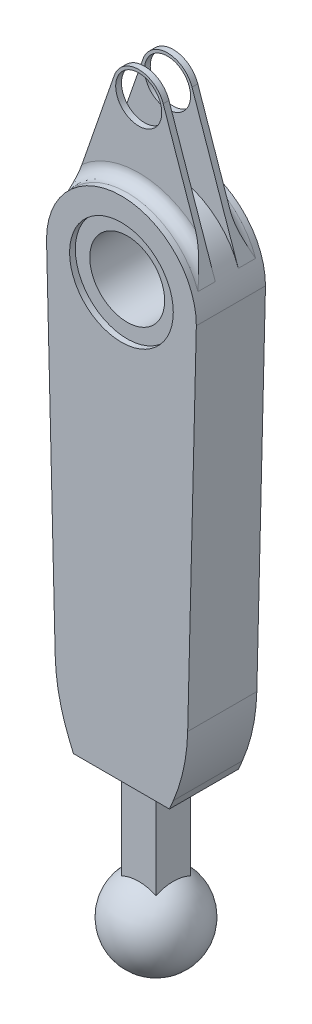
SolidWorks part; units mm, degrees
ref_plane "Front Plane" through (0, 0, 0) normal (0, 0, 1) x (1, 0, 0)
ref_plane "Top Plane" through (0, 0, 0) normal (0, 1, 0) x (1, 0, 0)
ref_plane "Right Plane" through (0, 0, 0) normal (1, 0, 0) x (0, 0, -1)
sketch "Sketch1" plane through (0, 0, 0) normal (0, 0, 1) x (1, 0, 0)
  line L0 (0, 0) -> (0, -50000) construction
  line L1 (-55, 0) -> (-47.5, -308.5609)
  line L2 (-35.7915, -363.12) -> (-35, -365)
  line L3 (35.7915, -363.12) -> (35, -365)
  line L4 (55, 0) -> (47.5, -308.5609)
  line L5 (-35, -365) -> (35, -365)
  line L6 (-21.7855, 135.625) -> (-53.2535, 13.75)
  line L7 (21.7855, 135.625) -> (53.2535, 13.75)
  circle A0 centre (0, 0) radius 55
  arc A1 (-47.5, -308.5609) -> (-35.7915, -363.12) centre (102.4557, -304.916) ccw
  arc A2 (47.5, -308.5609) -> (35.7915, -363.12) centre (-102.4557, -304.916) cw
  circle A3 centre (0, 130) radius 22.5
  circle A4 centre (0, 0) radius 45
  dimension "D1" = 110
  dimension "D2" = 365
  dimension "D4" = 150
  dimension "D7" = 45
  dimension "D9" = 90
  dimension "D3" = 70
  dimension "D5" = 95
  dimension "D6" = 308.5609
  dimension "D8" = 130
extrude "Boss-Extrude1" add sketch "Sketch1" along normal mid plane 10 contours A0 L0 L5 L3 A2 L4 | L0 A0 L1 A1 L2 L5 | L0 A0 L1 A4 | A0 L0 A4 L4 region at (-36.8614, -38.698, 0) region at (25.416, -197.9296, 0) region at (-25.416, -197.9296, 0)
sketch "Sketch3" plane through (0, 0, 5) normal (0, 0, 1) x (1, 0, 0)
  line L0 (35.7915, -363.12) -> (35, -365) construction
  line L1 (-35.7915, -363.12) -> (-35, -365) construction
  line L2 (-35, -365) -> (35, -365) construction
  line L3 (-55, 0) -> (-47.5, -308.5609) construction
  line L4 (55, 0) -> (47.5, -308.5609) construction
  line L5 (35.7915, -363.12) -> (35, -365)
  line L6 (-35.7915, -363.12) -> (-35, -365)
  line L7 (-35, -365) -> (35, -365)
  line L8 (-55, 0) -> (-47.5, -308.5609)
  line L9 (55, 0) -> (47.5, -308.5609)
  line L10 (45.008, -367.0003) -> (41.64, -375)
  line L11 (-41.64, -375) -> (41.64, -375)
  line L12 (-45.008, -367.0003) -> (-41.64, -375)
  line L13 (-64.9999, -0.1266) -> (-57.497, -308.8039)
  line L14 (64.9999, -0.1266) -> (57.497, -308.8039)
  arc A0 (35.7915, -363.12) -> (47.5, -308.5609) centre (-102.4557, -304.916) ccw construction
  arc A1 (-47.5, -308.5609) -> (-35.7915, -363.12) centre (102.4557, -304.916) ccw construction
  arc A2 (55, 0) -> (-55, 0) centre (0, 0) ccw construction
  arc A3 (35.7915, -363.12) -> (47.5, -308.5609) centre (-102.4557, -304.916) ccw
  arc A4 (-47.5, -308.5609) -> (-35.7915, -363.12) centre (102.4557, -304.916) ccw
  arc A5 (55, 0) -> (-55, 0) centre (0, 0) ccw
  arc A6 (-57.497, -308.8039) -> (-45.008, -367.0003) centre (102.4557, -304.916) ccw
  arc A7 (64.9999, -0.1266) -> (-64.9999, -0.1266) centre (0, 0) ccw
  arc A8 (45.008, -367.0003) -> (57.497, -308.8039) centre (-102.4557, -304.916) ccw
  dimension "D1" = 10
extrude "Boss-Extrude5" add sketch "Sketch3" against normal blind 60
sketch "Sketch6" plane through (0, 0, -55) normal (0, 0, -1) x (-1, 0, 0)
  line L0 (-35.7915, -363.12) -> (-35, -365) construction
  line L1 (35, -365) -> (-35, -365) construction
  line L2 (35.7915, -363.12) -> (35, -365) construction
  line L3 (55, 0) -> (47.5, -308.5609) construction
  line L4 (-47.5, -308.5609) -> (-55, 0) construction
  line L5 (-35.7915, -363.12) -> (-35, -365)
  line L6 (35, -365) -> (-35, -365)
  line L7 (35.7915, -363.12) -> (35, -365)
  line L8 (55, 0) -> (47.5, -308.5609)
  line L9 (-47.5, -308.5609) -> (-55, 0)
  arc A0 (35.7915, -363.12) -> (47.5, -308.5609) centre (-102.4557, -304.916) ccw construction
  arc A1 (-47.5, -308.5609) -> (-35.7915, -363.12) centre (102.4557, -304.916) ccw construction
  arc A2 (55, 0) -> (-55, 0) centre (0, 0) ccw construction
  circle A3 centre (0, 0) radius 45 construction
  arc A4 (35.7915, -363.12) -> (47.5, -308.5609) centre (-102.4557, -304.916) ccw
  arc A5 (-47.5, -308.5609) -> (-35.7915, -363.12) centre (102.4557, -304.916) ccw
  arc A6 (55, 0) -> (-55, 0) centre (0, 0) ccw
  circle A7 centre (0, 0) radius 45
extrude "Boss-Extrude6" add sketch "Sketch6" against normal blind 10
sketch "Sketch7" plane through (0, 0, -45) normal (0, 0, 1) x (1, 0, 0)
  circle A0 centre (0, 0) radius 45 construction
  circle A1 centre (0, 0) radius 45
extrude "Boss-Extrude7" add sketch "Sketch7" against normal blind 5
ref_plane "Plane2" through (0, 0, -5) normal (0, 0, -1) x (-1, 0, 0)
sketch "Sketch8" plane through (0, 0, -5) normal (0, 0, -1) x (-1, 0, 0)
  circle A0 centre (0, 0) radius 45 construction
  circle A1 centre (0, 0) radius 45
extrude "Boss-Extrude8" add sketch "Sketch8" against normal blind 5
ref_plane "Plane3" through (0, 0, -25) normal (0, 0, -1) x (-1, 0, 0)
sketch "Sketch9" plane through (0, 0, -25) normal (0, 0, -1) x (-1, 0, 0)
  line L1 (35.7915, -363.12) -> (35, -365) construction
  line L8 (35.7915, -363.12) -> (35, -365)
  line L9 (-21.2636, 137.3558) -> (-61.4283, 21.25)
  line L10 (21.2636, 137.3558) -> (61.4283, 21.25)
  circle A1 centre (0, 130) radius 22.5
  circle A2 centre (0, 130) radius 22.5
  arc A3 (64.9999, -0.1266) -> (-64.9999, -0.1266) centre (0, 0) ccw construction
  arc A5 (61.4283, 21.25) -> (-61.4283, 21.25) centre (0, 0) ccw
  dimension "D1" = 0
extrude "Boss-Extrude9" add sketch "Sketch9" along normal mid plane 30 contours A5 L10 A2 L9 | A2 L10 region at (0, 82.8235, -25) region at (0, 130, -25)
fillet "Fillet1" radius 10 2 edges at (0, 65, -40) (0, 65, -10)
sketch "Sketch13" plane through (0, 0, 0) normal (0, 0, 1) x (1, 0, 0)
  circle A0 centre (0, 0) radius 32.5
  circle A1 centre (0, 0) radius 37.5
  dimension "D1" = 65
  dimension "D2" = 75
extrude "Boss-Extrude11" add sketch "Sketch13" against normal up to surface (50 mm away) contours A0 | A1 up to face at (45, 0, -50)
sketch "Sketch14" plane through (0, 0, 0) normal (0, 0, 1) x (1, 0, 0)
  circle A0 centre (0, 0) radius 32.5
  dimension "D1" = 65
extrude "Cut-Extrude2" cut sketch "Sketch14" against normal through all
sketch "Sketch15" plane through (0, 0, -25) normal (0, 0, -1) x (-1, 0, 0)
  line L0 (-21.2636, 137.3558) -> (-61.4283, 21.25) construction
  line L1 (21.2636, 137.3558) -> (61.4283, 21.25) construction
  line L2 (35.7915, -363.12) -> (35, -365) construction
  line L3 (-21.2636, 137.3558) -> (-61.4283, 21.25)
  line L4 (21.2636, 137.3558) -> (61.4283, 21.25)
  line L5 (35.7915, -363.12) -> (35, -365)
  arc A0 (61.4283, 21.25) -> (-61.4283, 21.25) centre (0, 0) ccw construction
  circle A1 centre (0, 130) radius 22.5
  arc A2 (21.2636, 137.3558) -> (-21.2636, 137.3558) centre (0, 130) ccw
  arc A3 (61.4283, 21.25) -> (-61.4283, 21.25) centre (0, 0) ccw
  dimension "D1" = 0
extrude "Cut-Extrude3" cut sketch "Sketch15" against normal mid plane 20 contours A3 L4 A2 L3 region at (0, 82.8235, -25) region at (0, 130, -25)
sketch "Sketch16" plane through (0, 0, -40) normal (0, 0, -1) x (-1, 0, 0)
  circle A0 centre (0, 130) radius 20
  dimension "D1" = 40
extrude "Cut-Extrude4" cut sketch "Sketch16" against normal blind 45
sketch "Sketch17" plane through (0, -375, 0) normal (0, -1, 0) x (1, 0, 0)
  line L0 (-41.64, -25) -> (41.64, -25) construction
  line L1 (-41.64, -55) -> (-41.64, 5) construction
  line L2 (41.64, -55) -> (41.64, 5) construction
  line L4 (-15, -40) -> (15, -40)
  line L5 (-15, -40) -> (-15, -10)
  line L6 (-15, -10) -> (15, -10)
  line L7 (15, -40) -> (15, -10)
  line L8 (-15, -40) -> (15, -10) construction
  line L9 (-15, -10) -> (15, -40) construction
  point P6 (0, -25)
extrude "Boss-Extrude12" add sketch "Sketch17" along normal blind 117
sketch "Sketch18" plane through (0, 0, -25) normal (0, 0, -1) x (-1, 0, 0)
  line L0 (15, -492) -> (-15, -492) construction
  line L1 (0, -454.5097) -> (0, -529.4903)
  arc A0 (0, -529.4903) -> (0, -454.5097) centre (0, -492) cw
revolve "Revolve1" add sketch "Sketch18" angle 360 about L1
ref_plane "Plane4" through (0, 0, -25) normal (0, 0, -1) x (-1, 0, 0)
